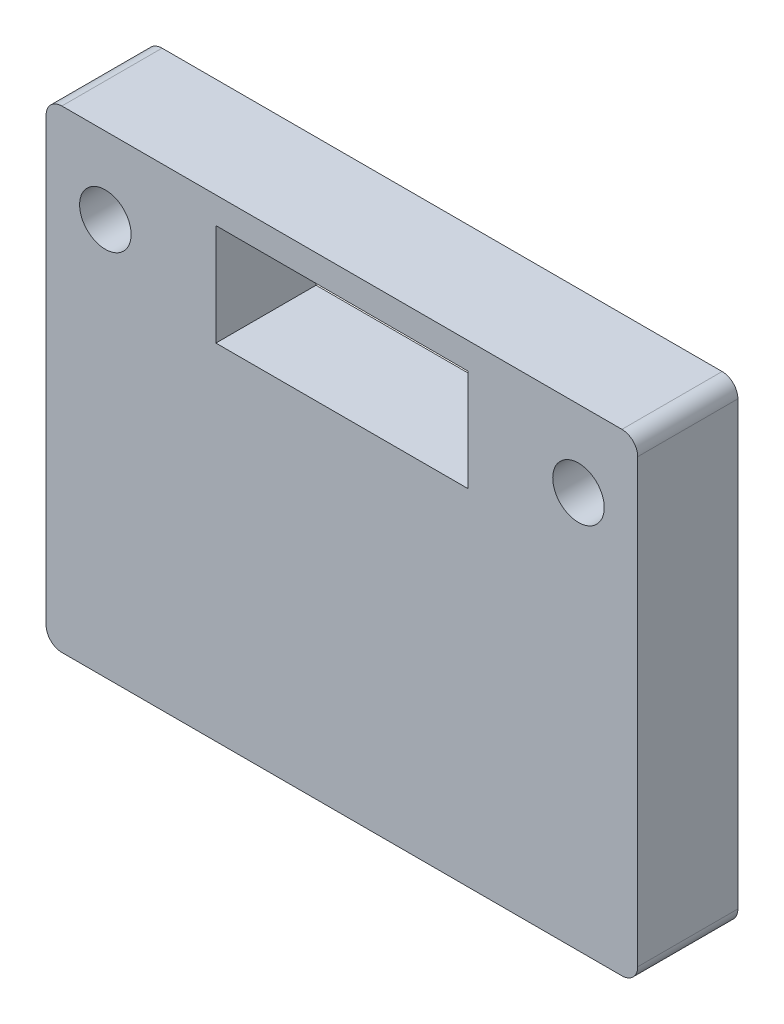
SolidWorks part; units mm, degrees
ref_plane "Front Plane" through (0, 0, 0) normal (0, 0, 1) x (1, 0, 0)
ref_plane "Top Plane" through (0, 0, 0) normal (0, 1, 0) x (1, 0, 0)
ref_plane "Right Plane" through (0, 0, 0) normal (1, 0, 0) x (0, 0, -1)
sketch "Sketch1" plane through (0, 0, 0) normal (0, 0, 1) x (1, 0, 0)
  line L0 (37.5, 0) -> (37.5, -60) construction
  line L1 (0, 0) -> (75, 0)
  line L2 (0, 0) -> (0, -60)
  line L3 (0, -60) -> (75, -60)
  line L4 (75, 0) -> (75, -60)
  line L5 (21.525, -3.3671) -> (21.525, -16.2671)
  line L6 (21.525, -16.2671) -> (53.475, -16.2671)
  line L7 (53.475, -16.2671) -> (53.475, -3.3671)
  line L9 (53.475, -3.3671) -> (37.5, -3.3671)
  line L10 (37.5, -3.3671) -> (21.525, -3.3671)
  dimension "D1" = 75
  dimension "D2" = 60
  dimension "D3" = 31.95
  dimension "D4" = 12.9
extrude "Boss-Extrude1" add sketch "Sketch1" along normal blind 12.7
sketch "Sketch2" plane through (0, 0, 0) normal (0, 0, -1) x (-1, 0, 0)
  line L1 (0, -9.7171) -> (-7.51, -9.7171)
  line L2 (-75, -60) -> (-75, 0) construction
  line L3 (-75, -9.7171) -> (-67.49, -9.7171)
  line L4 (0, 0) -> (0, -60) construction
  dimension "D1" = 7.51
  dimension "D2" = 7.51
hole_wizard "CSK for 1/4 Flat Head Machine Screw1" positions "Sketch3" profile "Sketch4" countersink size "1/4" standard "ANSI Inch" end condition through all
sketch "Sketch3" plane through (0, 0, 0) normal (0, 0, -1) x (-1, 0, 0)
  point P0 (-67.49, -9.7171)
  point P3 (-7.51, -9.7171)
sketch "Sketch4" plane through (67.49, -9.7171, 0) normal (1, 0, 0) x (0, 1, 0)
  line L0 (0, 0) -> (0, 12.7)
  line L1 (0, 12.7) -> (3.2639, 12.7)
  line L2 (3.2639, 12.7) -> (3.2639, 3.6524)
  line L3 (3.2639, 3.6524) -> (6.4389, 0)
  line L5 (6.4389, 0) -> (0, 0)
  line L6 (-3.2639, 3.6524) -> (-6.4389, 0) construction
  line L11 (0, -6.35) -> (0, 107.95) construction
  dimension "Thru Hole Dia." = 6.5278
  dimension "Thru Hole Depth" = 12.7
  dimension "Near C'Sink Dia." = 12.8778
  dimension "Near C'Sink Angle" = 82
fillet "Fillet1" radius 2 4 edges at (0, -60, 6.35) (0, 0, 6.35) (75, 0, 6.35) (75, -60, 6.35)
